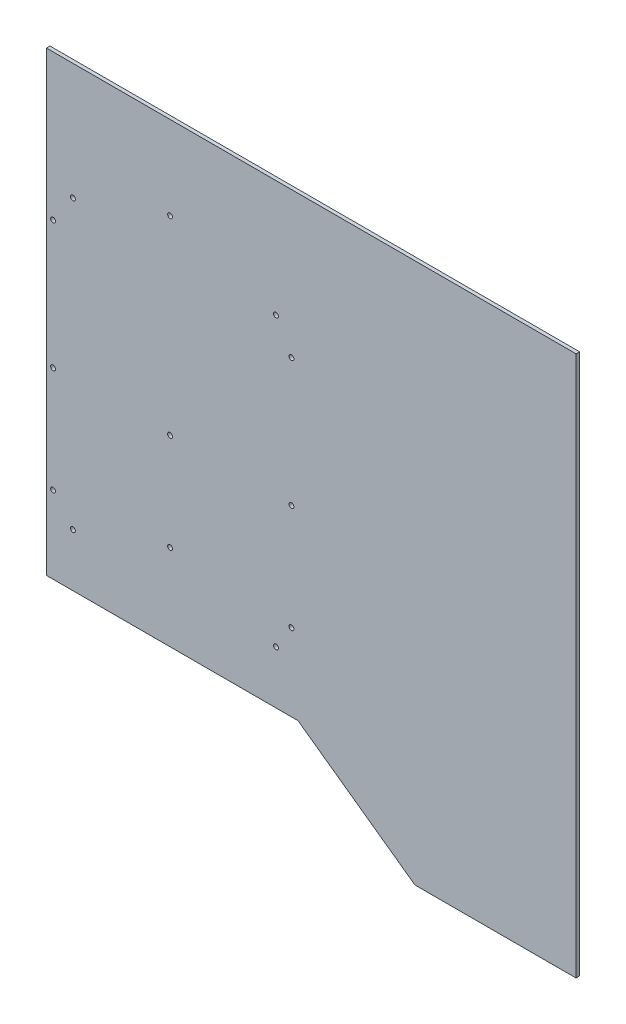
SolidWorks part; units mm, degrees
ref_plane "Piano frontale" through (0, 0, 0) normal (0, 0, 1) x (1, 0, 0)
ref_plane "Piano superiore" through (0, 0, 0) normal (0, 1, 0) x (1, 0, 0)
ref_plane "Piano destro" through (0, 0, 0) normal (1, 0, 0) x (0, 0, -1)
sketch "Schizzo1" plane through (0, 0, 0) normal (0, 0, 1) x (1, 0, 0)
  line L0 (0, 1191.9662) -> (0, -1214.0397) construction
  line L1 (-1195.7704, 0) -> (1209.3057, 0) construction
  line L2 (-600, 600) -> (600, 600)
  line L3 (600, 600) -> (600, -625)
  line L4 (600, -625) -> (235, -625)
  line L5 (235, -625) -> (-30, -435)
  line L6 (-30, -435) -> (-600, -435)
  line L7 (-600, -435) -> (-600, 600)
  dimension "D1" = 600
  dimension "D2" = 600
  dimension "D3" = 600
  dimension "D4" = 625
  dimension "D5" = 190
  dimension "D6" = 265
  dimension "D7" = 365
extrude "Estrusione-Estrusione1" add sketch "Schizzo1" along normal blind 8
sketch "Schizzo2" plane through (0, 0, 8) normal (0, 0, 1) x (1, 0, 0)
  line L0 (-44.8723, 384.4382) -> (-44.8723, -291.3431) construction
  line L1 (-585, -20) -> (-44.8723, -20) construction
  line L2 (-585, 391.4132) -> (-585, -291.3431) construction
  line L3 (-540, 543.4582) -> (-540, -331.0418) construction
  line L4 (-319.8723, 543.4582) -> (-319.8723, -331.0418) construction
  line L5 (-79.8723, 543.4582) -> (-79.8723, -331.0418) construction
  line L6 (-585, -260) -> (-44.8723, -260) construction
  line L7 (-540, -315) -> (-79.8723, -315) construction
  line L8 (-540, 336) -> (-79.8723, 336) construction
  line L9 (-585, 270) -> (-44.8723, 270) construction
  line L10 (-600, -435) -> (-30, -435) construction
  line L11 (-600, 600) -> (-600, -435) construction
  line L12 (-319.8723, 411) -> (-319.8723, -20) construction
  line L13 (-319.8723, -20) -> (-319.8723, -240) construction
  circle A0 centre (-585, -260) radius 5.5
  circle A1 centre (-540, -315) radius 5.5
  circle A4 centre (-79.8723, -315) radius 5.5
  circle A5 centre (-44.8723, -260) radius 5.5
  circle A6 centre (-44.8723, -20) radius 5.5
  circle A7 centre (-79.8723, 336) radius 5.5
  circle A8 centre (-540, 336) radius 5.5
  circle A9 centre (-585, -20) radius 5.5
  circle A10 centre (-585, 270) radius 5.5
  circle A11 centre (-44.8723, 270) radius 5.5
  circle A12 centre (-319.8723, 411) radius 5.5
  circle A13 centre (-319.8723, -20) radius 5.5
  circle A14 centre (-319.8723, -240) radius 5.5
  dimension "D1" = 55
  dimension "D2" = 120
  dimension "D3" = 15
  dimension "D4" = 45
  dimension "D5" = 220.1277
  dimension "D6" = 35
  dimension "D7" = 240
  dimension "D8" = 240
  dimension "D9" = 290
  dimension "D10" = 66
  dimension "D11" = 11
  dimension "D12" = 11
  dimension "D13" = 11
  dimension "D14" = 11
  dimension "D15" = 11
  dimension "D16" = 11
  dimension "D17" = 11
  dimension "D18" = 11
  dimension "D19" = 11
  dimension "D20" = 11
  dimension "D21" = 11
  dimension "D22" = 11
  dimension "D23" = 11
extrude "Taglio-Estrusione1" cut sketch "Schizzo2" against normal up to surface (8 mm away) up to face at (34.1667, -153.3333, 0)
